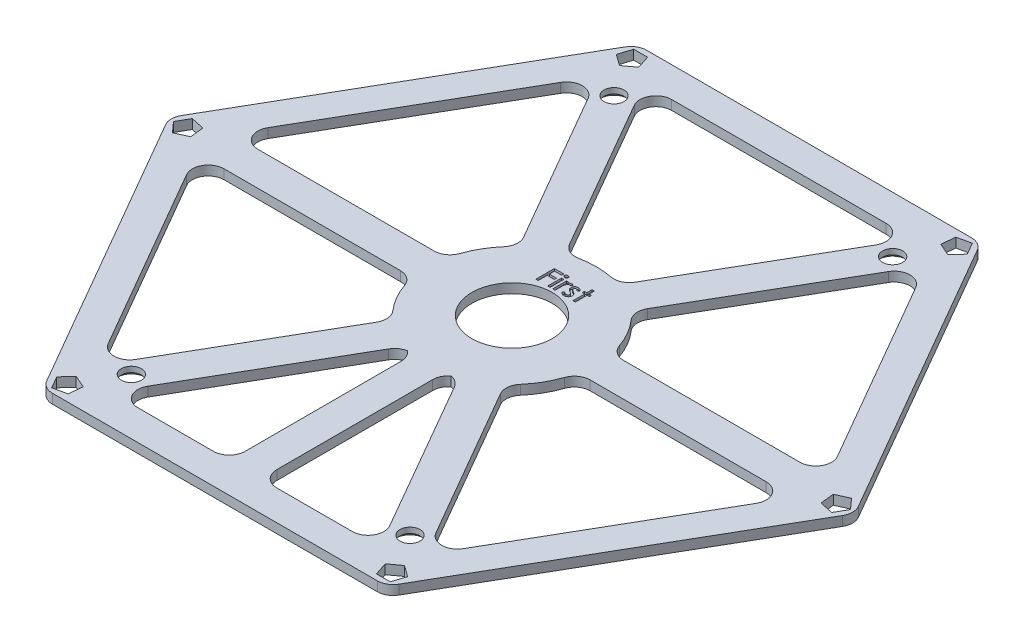
SolidWorks part; units mm, degrees
ref_plane "Front Plane" through (0, 0, 0) normal (0, 0, 1) x (1, 0, 0)
ref_plane "Top Plane" through (0, 0, 0) normal (0, 1, 0) x (1, 0, 0)
ref_plane "Right Plane" through (0, 0, 0) normal (1, 0, 0) x (0, 0, -1)
sketch "Sketch1" plane through (0, 0, 0) normal (0, 1, 0) x (1, 0, 0)
  line L0 (-30.85, 53.4338) -> (-30.85, 42.7905) construction
  line L1 (-32.5, 56.2917) -> (-65, 0)
  line L2 (-65, 0) -> (-32.5, -56.2917)
  line L3 (-32.5, -56.2917) -> (32.5, -56.2917)
  line L4 (32.5, -56.2917) -> (65, 0)
  line L5 (65, 0) -> (32.5, 56.2917)
  line L6 (32.5, 56.2917) -> (-32.5, 56.2917)
  line L7 (-31.05, 47.3716) -> (-56.55, 3.2043)
  line L8 (-56.55, -3.2043) -> (-31.05, -47.3716)
  line L9 (-25.5, -50.5759) -> (-3, -50.5759)
  line L10 (31.05, -47.3716) -> (56.55, -3.2043)
  line L11 (56.55, 3.2043) -> (31.05, 47.3716)
  line L12 (25.5, 50.5759) -> (-25.5, 50.5759)
  line L13 (-30.85, 53.4338) -> (-61.7, 0) construction
  line L14 (-61.7, 0) -> (-30.85, -53.4338) construction
  line L15 (-30.85, -53.4338) -> (30.85, -53.4338) construction
  line L16 (30.85, -53.4338) -> (61.7, 0) construction
  line L17 (61.7, 0) -> (30.85, 53.4338) construction
  line L18 (30.85, 53.4338) -> (-30.85, 53.4338) construction
  line L50 (28.9265, 52.3155) -> (31.3192, 51.2589)
  line L51 (-30.8433, 51.2089) -> (-28.7319, 52.7526)
  line L52 (-28.7319, 52.7526) -> (-29.5477, 55.2377)
  line L58 (-31.05, 47.3716) -> (-10.6129, 11.9735)
  line L60 (25.5, 50.5759) -> (5.0629, 15.1778)
  line L66 (56.55, 3.2043) -> (15.6759, 3.2043)
  line L72 (31.05, -47.3716) -> (10.6129, -11.9735)
  line L78 (-25.5, -50.5759) -> (-5.0629, -15.1778)
  line L84 (-56.55, -3.2043) -> (-15.6759, -3.2043)
  line L89 (-5.1089, 15.1624) -> (-25.5, 50.5759)
  line L91 (-29.5477, 55.2377) -> (-32.1632, 55.2298)
  line L92 (10.5766, 12.0056) -> (31.05, 47.3716)
  line L94 (-32.1632, 55.2298) -> (-32.9639, 52.7398)
  line L95 (15.6855, -3.1568) -> (56.55, -3.2043)
  line L97 (-32.9639, 52.7398) -> (-30.8433, 51.2089)
  line L98 (5.1089, -15.1624) -> (25.5, -50.5759)
  line L100 (31.3192, 51.2589) -> (33.0634, 53.2079)
  line L101 (-10.6129, -11.9735) -> (-31.05, -47.3716)
  line L103 (33.0634, 53.2079) -> (31.7488, 55.4691)
  line L104 (-15.6759, 3.2043) -> (-56.55, 3.2043)
  line L106 (31.7488, 55.4691) -> (29.1921, 54.9175)
  line L107 (29.1921, 54.9175) -> (28.9265, 52.3155)
  line L108 (59.7698, 1.1066) -> (60.0511, -1.4938)
  line L109 (60.0511, -1.4938) -> (62.6111, -2.0298)
  line L110 (62.6111, -2.0298) -> (63.912, 0.2393)
  line L111 (63.912, 0.2393) -> (62.156, 2.1777)
  line L112 (62.156, 2.1777) -> (59.7698, 1.1066)
  line L113 (30.8433, -51.2089) -> (28.7319, -52.7526)
  line L114 (28.7319, -52.7526) -> (29.5477, -55.2377)
  line L115 (29.5477, -55.2377) -> (32.1632, -55.2298)
  line L116 (32.1632, -55.2298) -> (32.9639, -52.7398)
  line L117 (32.9639, -52.7398) -> (30.8433, -51.2089)
  line L118 (-28.9265, -52.3155) -> (-31.3192, -51.2589)
  line L119 (-31.3192, -51.2589) -> (-33.0634, -53.2079)
  line L120 (-33.0634, -53.2079) -> (-31.7488, -55.4691)
  line L121 (-31.7488, -55.4691) -> (-29.1921, -54.9175)
  line L122 (-29.1921, -54.9175) -> (-28.9265, -52.3155)
  line L123 (-59.7698, -1.1066) -> (-60.0511, 1.4938)
  line L124 (-60.0511, 1.4938) -> (-62.6111, 2.0298)
  line L125 (-62.6111, 2.0298) -> (-63.912, -0.2393)
  line L126 (-63.912, -0.2393) -> (-62.156, -2.1777)
  line L127 (-62.156, -2.1777) -> (-59.7698, -1.1066)
  line L128 (0, 0) -> (0, -56.2917) construction
  line L129 (-30.85, 53.4338) -> (30.85, -53.4338) construction
  line L134 (3, -50.5759) -> (25.5, -50.5759)
  line L135 (30.85, 53.4338) -> (-30.85, -53.4338) construction
  line L136 (3, -50.5759) -> (3, -15.7162)
  line L138 (-3, -50.5759) -> (-3, -15.7162)
  line L143 (27.35, -47.3716) -> (-27.35, 47.3716) construction
  line L144 (27.35, 47.3716) -> (-27.35, -47.3716) construction
  circle A0 centre (0, 0) radius 56.2917 construction
  circle A1 centre (0, 0) radius 50.5759 construction
  circle A2 centre (0, 0) radius 53.4338 construction
  circle A3 centre (-30.85, 53.4338) radius 1.8 construction
  arc A4 (-10.6129, 11.9735) -> (-15.6759, 3.2043) centre (0, 0) ccw
  arc A5 (5.0629, 15.1778) -> (-5.1089, 15.1624) centre (0, 0) ccw
  arc A6 (15.6759, 3.2043) -> (10.5766, 12.0056) centre (0, 0) ccw
  arc A7 (10.6129, -11.9735) -> (15.6855, -3.1568) centre (0, 0) ccw
  arc A8 (-5.0629, -15.1778) -> (-3, -15.7162) centre (0, 0) ccw
  arc A9 (-15.6759, -3.2043) -> (-10.6129, -11.9735) centre (0, 0) ccw
  arc A10 (3, -15.7162) -> (5.1089, -15.1624) centre (0, 0) ccw
  circle A17 centre (0, 0) radius 52.8 construction
  circle A18 centre (-26.4, 45.7261) radius 1.9
  circle A19 centre (26.4, 45.7261) radius 1.9
  circle A20 centre (26.4, -45.7261) radius 1.9
  circle A21 centre (-26.4, -45.7261) radius 1.9
  point P27 (0, -35.2882)
  point P53 (0, 0)
  point P58 (-0.0078, -0.0152)
  point P70 (0, 0)
  point P87 (0, 0)
  dimension "D5" = 54.7
  dimension "D1" = 65
  dimension "D2" = 30
  dimension "D3" = 3.3
  dimension "D4" = 6
  dimension "D6" = 94.7432
  dimension "D7" = 6
  dimension "D9" = 60
extrude "Boss-Extrude1" add sketch "Sketch1" along normal blind 1.8
fillet "Fillet1" radius 3 6 edges at (-65, 0.9, 0) (-32.5, 0.9, 56.2917) (32.5, 0.9, 56.2917) (65, 0.9, 0) (32.5, 0.9, -56.2917) (-32.5, 0.9, -56.2917)
sketch "Sketch2" plane through (0, 0, 0) normal (0, 1, 0) x (1, 0, 0)
fillet "Fillet2" radius 3 28 edges at (-25.5, 0.9, 50.5759) (31.05, 0.9, 47.3716) (-31.05, 0.9, 47.3716) (-56.55, 0.9, 3.2043) (-15.6759, 0.9, 3.2043) (-10.6129, 0.9, 11.9735) (-31.05, 0.9, -47.3716) (-56.55, 0.9, -3.2043) (-15.6759, 0.9, -3.2043) (-10.6129, 0.9, -11.9735) (-25.5, 0.9, -50.5759) (25.5, 0.9, -50.5759) (56.55, 0.9, -3.2043) (56.55, 0.9, 3.2043) (31.05, 0.9, -47.3716) (-5.0629, 0.9, 15.1778) (10.6129, 0.9, 11.9735) (15.6855, 0.9, 3.1568) (15.6759, 0.9, -3.2043) (10.5766, 0.9, -12.0056) (5.0629, 0.9, -15.1778) (-5.1089, 0.9, -15.1624) (3, 0.9, 50.5759) (-3, 0.9, 50.5759) (25.5, 0.9, 50.5759) (5.1089, 0.9, 15.1624) (3, 0.9, 15.7162) (-3, 0.9, 15.7162)
ref_plane "Plane1" through (0, 3.6, 0) normal (0, 1, 0) x (1, 0, 0)
sketch "Sketch3" plane through (0, 3.6, 0) normal (0, 1, 0) x (1, 0, 0)
  circle A0 centre (0, 0) radius 7.6
extrude "Cut-Extrude1" cut sketch "Sketch3" against normal blind 10
ref_plane "Plane2" through (0, 1.8, 0) normal (0, 1, 0) x (1, 0, 0)
sketch "Sketch4" plane through (0, 1.8, 0) normal (0, 1, 0) x (1, 0, 0)
  line L0 (-11.0192, 8.222) -> (11.0192, 8.222) construction
  text T0 "<b>First</b>"
extrude "Cut-Extrude2" cut sketch "Sketch4" against normal blind 0.4
ref_plane "Plane3" through (0, 0, 0) normal (0, -1, 0) x (-1, 0, 0)
sketch "Sketch5" plane through (0, 0, 0) normal (0, -1, 0) x (-1, 0, 0)
  line L5 (21.5, -37.4) -> (-21.5, 37.4) construction
  line L6 (21.5, 37.4) -> (-21.5, -37.4) construction
  point P0 (0, 0)
  dimension "D1" = 43
  dimension "D2" = 74.8
chamfer "Chamfer1" distance 0.75 angle 45 4 edges at (-26.4, 0, 47.6261) (26.4, 0, 47.6261) (-26.4, 0, -43.8261) (26.4, 0, -43.8261)
scale "Scale1" scale about centroid uniform scaling yes scale factor 1.15
